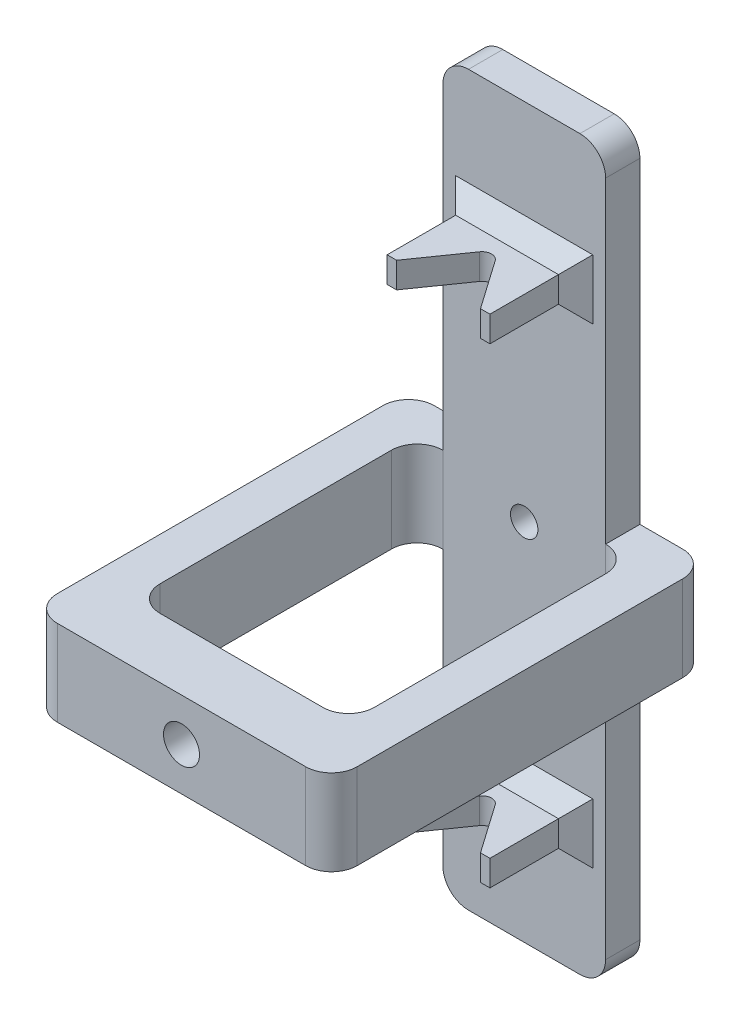
SolidWorks part; units mm, degrees
ref_plane "Front Plane" through (0, 0, 0) normal (0, 0, 1) x (1, 0, 0)
ref_plane "Top Plane" through (0, 0, 0) normal (0, 1, 0) x (1, 0, 0)
ref_plane "Right Plane" through (0, 0, 0) normal (1, 0, 0) x (0, 0, -1)
sketch "Sketch1" plane through (0, 0, 0) normal (0, 0, 1) x (1, 0, 0)
  line L1 (-7.5, 42.5) -> (7.5, 42.5)
  line L2 (-7.5, 42.5) -> (-7.5, -42.5)
  line L3 (-7.5, -42.5) -> (7.5, -42.5)
  line L4 (7.5, 42.5) -> (7.5, -42.5)
  line L5 (-7.5, 42.5) -> (7.5, -42.5) construction
  line L6 (-7.5, -42.5) -> (7.5, 42.5) construction
  point P0 (0, 0)
  dimension "D1" = 85
  dimension "D2" = 15
extrude "Boss-Extrude1" add sketch "Sketch1" along normal blind 4
sketch "Sketch2" plane through (0, 0, 4) normal (0, 0, 1) x (1, 0, 0)
  line L0 (0, 42.5) -> (0, 27.5)
  line L1 (0, -42.5) -> (0, -27.5)
  line L3 (-6, 29) -> (6, 29)
  line L4 (7.5, -42.5) -> (7.5, 42.5)
  line L5 (7.5, 42.5) -> (-7.5, 42.5)
  line L6 (-7.5, 42.5) -> (-7.5, -42.5)
  line L7 (-7.5, -42.5) -> (7.5, -42.5)
  line L9 (7.5, 42.5) -> (-7.5, 42.5)
  line L11 (-7.5, -42.5) -> (7.5, -42.5)
  line L12 (-6, 29) -> (-6, 26)
  line L13 (-6, 26) -> (6, 26)
  line L14 (6, 29) -> (6, 26)
  line L15 (-6, 29) -> (6, 26) construction
  line L16 (-6, 26) -> (6, 29) construction
  line L17 (-6, -29) -> (6, -29)
  line L18 (-6, -29) -> (-6, -26)
  line L19 (-6, -26) -> (6, -26)
  line L20 (6, -29) -> (6, -26)
  line L21 (-6, -29) -> (6, -26) construction
  line L22 (-6, -26) -> (6, -29) construction
  dimension "D2" = 15
  dimension "D3" = 15
  dimension "D4" = 3
  dimension "D5" = 12
  dimension "D6" = 3
  dimension "D7" = 12
  dimension "D1" = 0
extrude "Boss-Extrude2" add sketch "Sketch2" along normal blind 10 contours L14 L3 L12 L13 | L17 L20 L19 L18 region at (3, 28.8763, 4) region at (-3, -28.8763, 4)
sketch "Sketch3" plane through (0, 29, 0) normal (0, 1, 0) x (1, 0, 0)
  line L0 (0, -14) -> (0, -7)
  line L1 (-0.9046, -8.2934) -> (-4.896, -14)
  line L2 (0.9046, -8.2934) -> (4.896, -14)
  line L4 (6, -4) -> (-6, -4)
  line L5 (-6, -4) -> (-6, -14)
  line L6 (-6, -14) -> (6, -14)
  line L7 (6, -14) -> (6, -4)
  line L8 (6, -4) -> (-6, -4)
  line L9 (-6, -4) -> (-6, -12.896)
  line L10 (-4.896, -14) -> (4.896, -14)
  line L11 (6, -12.896) -> (6, -4)
  arc A0 (6, -12.896) -> (4.896, -14) centre (4.896, -12.896) cw
  arc A1 (-4.896, -14) -> (-6, -12.896) centre (-4.896, -12.896) cw
  arc A2 (0.9046, -8.2934) -> (-0.9046, -8.2934) centre (0, -8.9261) ccw
  line M9 (-6, -14) -> (6, -14)
  dimension "D2" = 1.104
  dimension "D4" = 1.104
  dimension "D3" = 7
  dimension "D1" = 0
extrude "Cut-Extrude1" cut sketch "Sketch3" against normal blind 60 contours L2 A2 L0 M9 | L0 A2 L1 M9 region at (-1.6555, 29, 11.7355) region at (1.6555, 29, 11.7355)
sketch "Sketch4" plane through (0, 0, 4) normal (0, 0, 1) x (1, 0, 0)
  line L0 (0, 0) -> (0, -15.4)
  circle A0 centre (0, -15.4) radius 1.6
  circle A1 centre (0, 0) radius 1.6
  dimension "D2" = 3.2
  dimension "D3" = 3.2
  dimension "D1" = 15.4
extrude "Cut-Extrude2" cut sketch "Sketch4" against normal blind 4 contours A1 | A0 region at (1.0994, -14.3006, 4) region at (-1.0994, 1.0994, 4)
sketch "Sketch5" plane through (0, 42.5, 0) normal (0, 1, 0) x (1, 0, 0)
  line L1 (7.5, 0) -> (17.5, 0)
  line L2 (7.5, 0) -> (7.5, -4)
  line L3 (7.5, -4) -> (17.5, -4)
  line L4 (17.5, 0) -> (17.5, -4)
  line L5 (-7.5, 0) -> (-17.5, 0)
  line L6 (-7.5, 0) -> (-7.5, -4)
  line L7 (-7.5, -4) -> (-17.5, -4)
  line L8 (-17.5, 0) -> (-17.5, -4)
  dimension "D1" = 10
  dimension "D2" = 10
  dimension "D3" = 4
  dimension "D4" = 4
extrude "Boss-Extrude3" add sketch "Sketch5" against normal blind 50
sketch "Sketch8" plane through (0, 0, 4) normal (0, 0, 1) x (1, 0, 0)
  line L1 (17.5, 42.5) -> (7.5, 42.5)
  line L2 (17.5, 42.5) -> (17.5, 2.5)
  line L3 (17.5, 2.5) -> (7.5, 2.5)
  line L4 (7.5, 42.5) -> (7.5, 2.5)
  line L5 (-17.5, 42.5) -> (-7.5, 42.5)
  line L6 (-17.5, 42.5) -> (-17.5, 2.5)
  line L7 (-17.5, 2.5) -> (-7.5, 2.5)
  line L8 (-7.5, 42.5) -> (-7.5, 2.5)
  dimension "D1" = 40
  dimension "D2" = 10
  dimension "D3" = 40
  dimension "D4" = 10
extrude "Cut-Extrude3" cut sketch "Sketch8" against normal blind 4
sketch "Sketch10" plane through (0, 0, 4) normal (0, 0, 1) x (1, 0, 0)
  line L1 (17.5, 2.5) -> (7.5, 2.5)
  line L2 (17.5, 2.5) -> (17.5, -7.5)
  line L3 (17.5, -7.5) -> (7.5, -7.5)
  line L4 (7.5, 2.5) -> (7.5, -7.5)
  line L5 (-17.5, 2.5) -> (-7.5, 2.5)
  line L6 (-17.5, 2.5) -> (-17.5, -7.5)
  line L7 (-17.5, -7.5) -> (-7.5, -7.5)
  line L8 (-7.5, 2.5) -> (-7.5, -7.5)
extrude "Boss-Extrude4" add sketch "Sketch10" along normal blind 40
sketch "Sketch11" plane through (7.5, 0, 0) normal (-1, 0, 0) x (0, 0, 1)
  line L1 (44, 2.5) -> (37, 2.5)
  line L2 (44, 2.5) -> (44, -7.5)
  line L3 (44, -7.5) -> (37, -7.5)
  line L4 (37, 2.5) -> (37, -7.5)
  dimension "D1" = 10
  dimension "D2" = 7
extrude "Boss-Extrude5" add sketch "Sketch11" along normal up to surface (15 mm away) up to face at (-7.5, -2.5, 24)
sketch "Sketch13" plane through (0, 2.5, 0) normal (0, 1, 0) x (1, 0, 0)
  line L3 (-7.5, -4) -> (-12.5, -4)
  line L4 (-7.5, -4) -> (-7.5, -37)
  line L5 (-7.5, -37) -> (-12.5, -37)
  line L6 (-12.5, -4) -> (-12.5, -37)
  line L7 (7.5, -4) -> (12.5, -4)
  line L8 (7.5, -4) -> (7.5, -37)
  line L9 (7.5, -37) -> (12.5, -37)
  line L10 (12.5, -4) -> (12.5, -37)
  dimension "D1" = 33
  dimension "D2" = 5
  dimension "D3" = 33
  dimension "D4" = 5
extrude "Cut-Extrude4" cut sketch "Sketch13" against normal blind 10
sketch "Sketch14" plane through (0, 0, 44) normal (0, 0, 1) x (1, 0, 0)
  line L0 (0, -7.5) -> (0, 2.5)
  line L1 (-17.5, -7.5) -> (17.5, -7.5) construction
  line L2 (17.5, 2.5) -> (-17.5, 2.5) construction
  circle A0 centre (0, -2.5) radius 2.1
  dimension "D1" = 4.2
extrude "Cut-Extrude6" cut sketch "Sketch14" against normal up to surface (7 mm away) contours L0 A0 | L0 A0 region at (-0.8913, -2.5, 44) region at (0.8913, -2.5, 44) up to face at (0, -2.5, 37)
sketch "Sketch17" plane through (7.5, 0, 0) normal (1, 0, 0) x (0, 0, -1)
  line L4 (0, -42.5) -> (0, -7.5)
  line L5 (0, -7.5) -> (-4, -7.5)
  line L6 (-4, -7.5) -> (-4, -42.5)
  line L7 (-4, -42.5) -> (0, -42.5)
  line L8 (0, -42.5) -> (0, -7.5)
  line L9 (0, -7.5) -> (-4, -7.5)
  line L10 (-4, -7.5) -> (-4, -42.5)
  line L11 (-4, -42.5) -> (0, -42.5)
  line L12 (-4, 42.5) -> (-4, 2.5)
  line L13 (-4, 2.5) -> (0, 2.5)
  line L14 (0, 2.5) -> (0, 42.5)
  line L15 (0, 42.5) -> (-4, 42.5)
  line L16 (-4, 42.5) -> (-4, 2.5)
  line L17 (-4, 2.5) -> (0, 2.5)
  line L18 (0, 2.5) -> (0, 42.5)
  line L19 (0, 42.5) -> (-4, 42.5)
  dimension "D1" = 0
  dimension "D2" = 0
extrude "Boss-Extrude6" add sketch "Sketch17" along normal blind 2
sketch "Sketch18" plane through (-7.5, 0, 0) normal (-1, 0, 0) x (0, 0, 1)
  line L4 (4, -42.5) -> (4, -7.5)
  line L5 (4, -7.5) -> (0, -7.5)
  line L6 (0, -7.5) -> (0, -42.5)
  line L7 (0, -42.5) -> (4, -42.5)
  line L8 (4, -42.5) -> (4, -7.5)
  line L9 (4, -7.5) -> (0, -7.5)
  line L10 (0, -7.5) -> (0, -42.5)
  line L11 (0, -42.5) -> (4, -42.5)
  line L12 (4, 2.5) -> (4, 42.5)
  line L13 (4, 42.5) -> (0, 42.5)
  line L14 (0, 42.5) -> (0, 2.5)
  line L15 (0, 2.5) -> (4, 2.5)
  line L16 (4, 2.5) -> (4, 42.5)
  line L17 (4, 42.5) -> (0, 42.5)
  line L18 (0, 42.5) -> (0, 2.5)
  line L19 (0, 2.5) -> (4, 2.5)
  dimension "D1" = 0
  dimension "D2" = 0
extrude "Boss-Extrude7" add sketch "Sketch18" along normal blind 2
fillet "Fillet2" radius 3 12 edges at (9.5, -42.5, 2) (-9.5, -42.5, 2) (9.5, 42.5, 2) (-9.5, 42.5, 2) (-17.5, -2.5, 0) (17.5, -2.5, 44) (-17.5, -2.5, 44) (12.5, -2.5, 37) (-12.5, -2.5, 37) (17.5, -2.5, 0) (12.5, -2.5, 4) (-12.5, -2.5, 4)
chamfer "Chamfer1" distance 2 angle 45 8 edges at (-6, -27.5, 4) (0, -26, 4) (6, -27.5, 4) (0, -29, 4) (0, 29, 4) (0, 26, 4) (-6, 27.5, 4) (6, 27.5, 4)
sketch "Sketch19" plane through (0, 0, 37) normal (0, 0, -1) x (-1, 0, 0)
  line L1 (4.0415, -2.5) -> (2.0207, 1)
  line L2 (2.0207, 1) -> (-2.0207, 1)
  line L3 (-2.0207, 1) -> (-4.0415, -2.5)
  line L4 (-4.0415, -2.5) -> (-2.0207, -6)
  line L5 (-2.0207, -6) -> (2.0207, -6)
  line L6 (2.0207, -6) -> (4.0415, -2.5)
  circle A0 centre (0, -2.5) radius 3.5 construction
  point P1 (0, 1)
  dimension "D1" = 7
